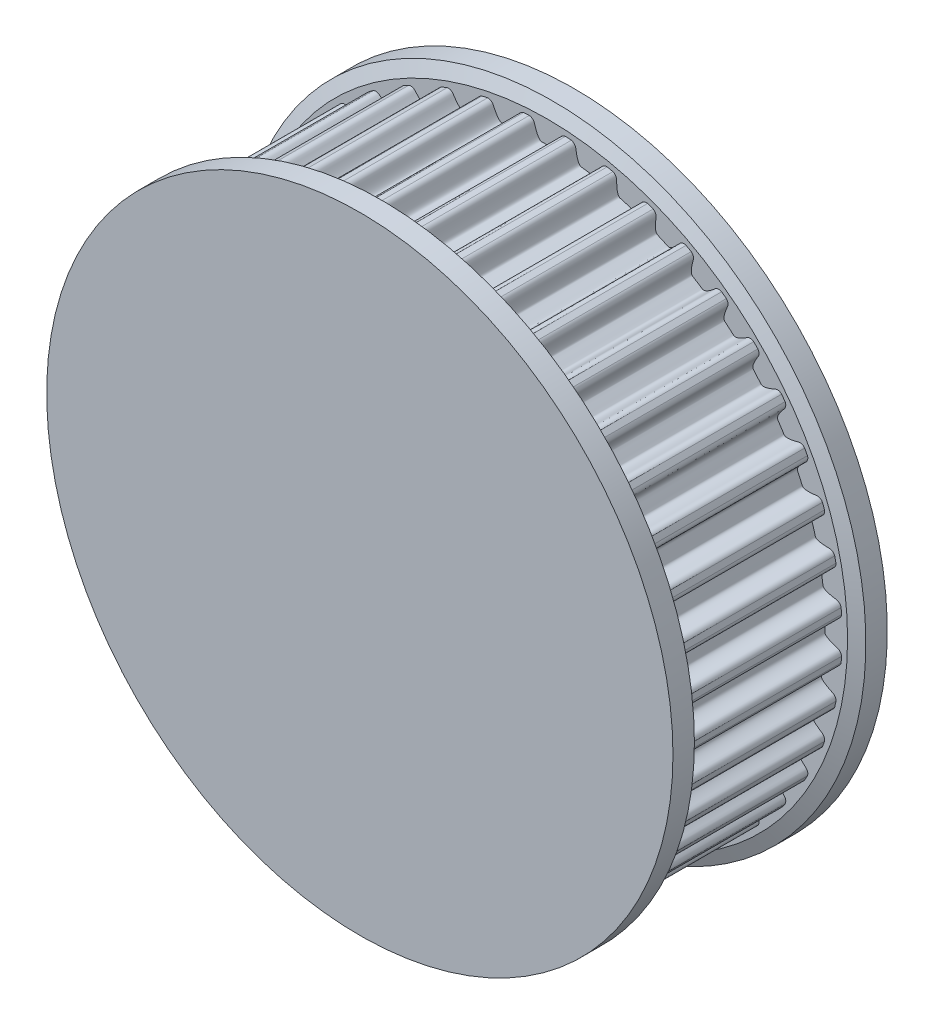
SolidWorks part; units mm, degrees
ref_plane "Front Plane" through (0, 0, 0) normal (0, 0, 1) x (1, 0, 0)
ref_plane "Top Plane" through (0, 0, 0) normal (0, 1, 0) x (1, 0, 0)
ref_plane "Right Plane" through (0, 0, 0) normal (1, 0, 0) x (0, 0, -1)
ref_axis "Axis1" through (0, 0, 55) along (0, 0, -1)
sketch "SketchRevolveGearBelt01" plane through (0, 0, 0) normal (1, 0, 0) x (0, 0, -1)
  line L0 (0, 0) -> (1, 0) construction
  line L1 (5.274, 0) -> (5.274, 12.5056)
  line L2 (5.274, 12.5056) -> (4.512, 12.5056)
  line L3 (4.512, 12.5056) -> (4.512, 13.8541)
  line L4 (4.512, 13.8541) -> (4.7696, 14.476)
  line L5 (4.7696, 14.476) -> (4.0656, 14.7676)
  line L6 (4.0656, 14.7676) -> (3.75, 14.0056)
  line L7 (3.75, 14.0056) -> (3.75, 13.7495)
  line L8 (3.75, 13.7495) -> (-3.75, 13.7495)
  line L9 (-3.75, 13.7495) -> (-3.75, 14.0056)
  line L10 (-3.75, 14.0056) -> (-4.0656, 14.7676)
  line L11 (-4.0656, 14.7676) -> (-4.7696, 14.476)
  line L12 (-4.7696, 14.476) -> (-4.512, 13.8541)
  line L13 (-4.512, 13.8541) -> (-4.512, 12.5056)
  line L14 (-4.512, 12.5056) -> (-5.274, 12.5056)
  line L15 (-5.274, 12.5056) -> (-5.274, 0)
  line L16 (-5.274, 0) -> (5.274, 0)
  dimension "GearBeltSide1" = 5.274
  dimension "GearBeltFlange1OutsideWidth" = 4.512
  dimension "GearBeltFlange1OutsideLength" = 1.3484
  dimension "GearBeltFlange1X" = 0.2576
  dimension "GearBeltFlange1Y" = 0.622
  dimension "GearBeltFlangeThickness" = 0.762
  dimension "GearBeltToothWidth1" = 3.75
  dimension "GearBeltFlangeInside" = 0.2561
  dimension "GearBeltOutsideDiameter" = 13.7495
  dimension "GearBeltToothWidth2" = 3.75
  dimension "GearBeltFlange2X" = 0.2576
  dimension "GearBeltFlange2OutsideWidth" = 4.512
revolve "GearBelt01" add sketch "SketchRevolveGearBelt01" angle 360 about L0
sketch "SketchToothGearBelt01" plane through (0, 0, 0) normal (0, 0, 1) x (1, 0, 0)
  arc A0 (13.7241, 0.8614) -> (13.7241, -0.8614) centre (0, 0) cw
  spline S0 degree 3 poles (13.7241, -0.8614) (13.7241, -0.8441) (13.7216, -0.8182) (13.7133, -0.7847) (13.7046, -0.7603) (13.6936, -0.7368) (13.6804, -0.7145) (13.6651, -0.6935) (13.6478, -0.6742) (13.6287, -0.6566) (13.6081, -0.641) (13.5859, -0.6275) (13.5627, -0.616) (13.5227, -0.6018) (13.4719, -0.5865) (13.4118, -0.5675) (13.3594, -0.5498) (13.3101, -0.5322) (13.264, -0.5145) (13.221, -0.4969) (13.1813, -0.4793) (13.1447, -0.4616) (13.1113, -0.444) (13.081, -0.4264) (13.0539, -0.4087) (13.03, -0.3911) (13.0092, -0.3735) (12.9916, -0.3558) (12.9771, -0.3381) (12.9658, -0.3203) (12.9577, -0.3025) (12.9527, -0.2846) (12.9505, -0.2503) (12.9537, -0.2) (12.9538, -0.1333) (12.9546, -0.0667) (12.9547, 0) (12.9546, 0.0667) (12.9538, 0.1333) (12.9537, 0.2) (12.9505, 0.2503) (12.9527, 0.2846) (12.9577, 0.3025) (12.9658, 0.3203) (12.9771, 0.3381) (12.9916, 0.3558) (13.0092, 0.3735) (13.03, 0.3911) (13.0539, 0.4087) (13.081, 0.4264) (13.1113, 0.444) (13.1447, 0.4616) (13.1813, 0.4793) (13.221, 0.4969) (13.264, 0.5145) (13.3101, 0.5322) (13.3594, 0.5498) (13.4118, 0.5675) (13.4719, 0.5865) (13.5227, 0.6018) (13.5627, 0.616) (13.5859, 0.6275) (13.6081, 0.641) (13.6287, 0.6566) (13.6478, 0.6742) (13.6651, 0.6935) (13.6804, 0.7145) (13.6936, 0.7368) (13.7046, 0.7603) (13.7133, 0.7847) (13.7216, 0.8182) (13.7241, 0.8441) (13.7241, 0.8614) knots 0 0 0 0 0.019761 0.029642 0.039523 0.049404 0.059284 0.069165 0.079046 0.088926 0.098807 0.108688 0.118569 0.128449 0.157158 0.17943 0.200549 0.220523 0.239359 0.257068 0.273661 0.289154 0.303565 0.316916 0.329236 0.340559 0.350934 0.360419 0.369094 0.377062 0.384456 0.39144 0.39821 0.423677 0.449118 0.474559 0.5 0.525441 0.550882 0.576323 0.60179 0.60856 0.615544 0.622938 0.630906 0.639581 0.649066 0.659441 0.670764 0.683084 0.696435 0.710846 0.726339 0.742932 0.760641 0.779477 0.799451 0.82057 0.842842 0.871551 0.881431 0.891312 0.901193 0.911074 0.920954 0.930835 0.940716 0.950596 0.960477 0.970358 0.980239 1 1 1 1
extrude "ToothExtrudeCutGearBelt01" cut sketch "SketchToothGearBelt01" against normal blind 3.75 and the other way blind 3.75
pattern_circular "PatternGearBelt01" count 44 every 8.182 about axis through (0, 0, 55) along (0, 0, -1) of "ToothExtrudeCutGearBelt01"
sketch "BoreRevolveSketch" plane through (0, 0, 0) normal (1, 0, 0) x (0, 0, -1)
  line L0 (0, 0) -> (1, 0) construction
  line L1 (-5.274, 0) -> (5.274, 0)
  line L2 (5.274, 0) -> (5.274, 5)
  line L3 (5.274, 5) -> (-5.274, 5)
  line L4 (-5.274, 5) -> (-5.274, 0)
  dimension "BoreSide1" = 5.274
  dimension "TaperSide1" = 5
  dimension "BoreSide2" = 5.274
  dimension "TaperSide2" = 5
revolve "BoreRevolveCut" cut sketch "BoreRevolveSketch" angle 360 about L0
sketch "AuxiliarySketchGearBelt01" plane through (0, 0, 0) normal (0, 0, 1) x (1, 0, 0)
  circle A0 centre (0, 0) radius 14.0056 construction
  dimension "PitchDiameter" = 28.0113
sketch "Sketch1" plane through (0, 0, 0) normal (0, 1, 0) x (1, 0, 0)
  line L0 (0, 0) -> (16.4312, 0) construction
  line L1 (18.6434, 9.4348) -> (-21.2303, 9.4348)
  line L2 (18.6434, 9.4348) -> (18.6434, 4)
  line L3 (18.6434, 4) -> (-21.2303, 4)
  line L4 (-21.2303, 9.4348) -> (-21.2303, 4)
  line L5 (18.6434, 9.4348) -> (-21.2303, 4) construction
  line L6 (18.6434, 4) -> (-21.2303, 9.4348) construction
  line L11 (18.6434, -9.4348) -> (-21.2303, -9.4348)
  line L12 (-21.2303, -9.4348) -> (-21.2303, -4)
  line L13 (18.6434, -4) -> (-21.2303, -4)
  line L14 (18.6434, -9.4348) -> (18.6434, -4)
  point P4 (-1.2935, 6.7174)
  dimension "D1" = 4
extrude "Cut-Extrude1" cut sketch "Sketch1" against normal through all both and the other way through all
sketch "Sketch2" plane through (0, 0, 4) normal (0, 0, 1) x (1, 0, 0)
  circle A1 centre (0, 0) radius 14.6092
  circle A2 centre (0, 0) radius 14.6092
  dimension "D1" = 0
extrude "Boss-Extrude1" add sketch "Sketch2" along normal blind 1
sketch "Sketch3" plane through (0, 0, -4) normal (0, 0, -1) x (-1, 0, 0)
  circle A1 centre (0, 0) radius 14.6092
  circle A2 centre (0, 0) radius 14.6092
  dimension "D1" = 0
extrude "Boss-Extrude2" add sketch "Sketch3" along normal blind 1
sketch "Sketch4" plane through (0, 0, 5) normal (0, 0, 1) x (1, 0, 0)
  circle A0 centre (0, 0) radius 8.5109
extrude "Boss-Extrude3" add sketch "Sketch4" against normal up to surface (10 mm away) up to face at (-14.6092, 0, -5)
